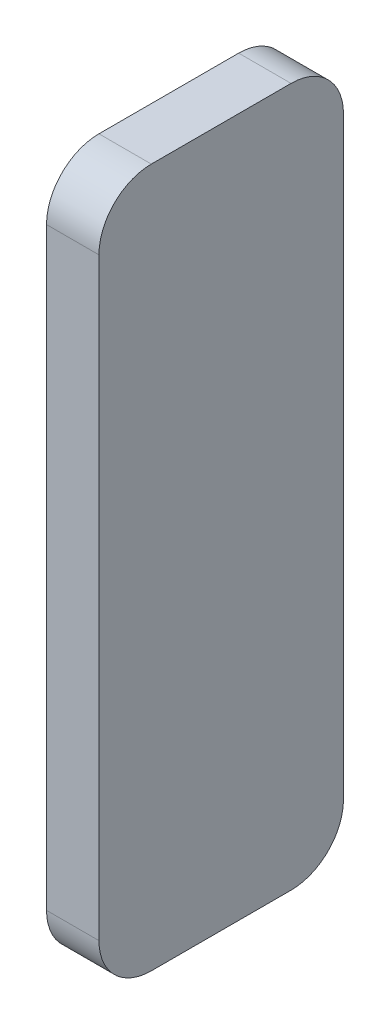
SolidWorks part; units mm, degrees
material "ABS"
ref_plane "Front Plane" through (0, 0, 0) normal (0, 0, 1) x (1, 0, 0)
ref_plane "Top Plane" through (0, 0, 0) normal (0, 1, 0) x (1, 0, 0)
ref_plane "Right Plane" through (0, 0, 0) normal (1, 0, 0) x (0, 0, -1)
sketch "Sketch1" plane through (0, 0, 0) normal (1, 0, 0) x (0, 0, -1)
  line L0 (0, 80) -> (0, -80) construction
  line L2 (-35, 100) -> (35, 100)
  line L3 (-35, 100) -> (-35, -100)
  line L4 (-35, -100) -> (35, -100)
  line L5 (35, 100) -> (35, -100)
  circle A0 centre (0, 80) radius 7.5
  circle A1 centre (0, -80) radius 7.5
  point P8 (0, 0)
  point P10 (-35, 0)
  point P11 (0, 100)
  point P12 (0, -100)
  point P13 (-10.7619, 19.5315)
  dimension "D1" = 15
  dimension "D2" = 70
  dimension "D3" = 200
  dimension "D4" = 160
extrude "Boss-Extrude1" add sketch "Sketch1" along normal blind 15 contours L5 L2 L3 L4 A0 A1 | A0 | A1 region at (0, 0, 0) region at (0, 80, 0) region at (0, -80, 0)
extrude "Cut-Extrude1" cut sketch "Sketch1<3>" along normal blind 5 contours A1 | A0 region at (0, -80, 0)
sketch "Sketch1<3>" plane through (0, 0, 0) normal (1, 0, 0) x (0, 0, -1) same geometry as "Sketch1"
fillet "Fillet1" radius 15 4 edges at (7.5, -100, -35) (7.5, -100, 35) (7.5, 100, -35) (7.5, 100, 35)
